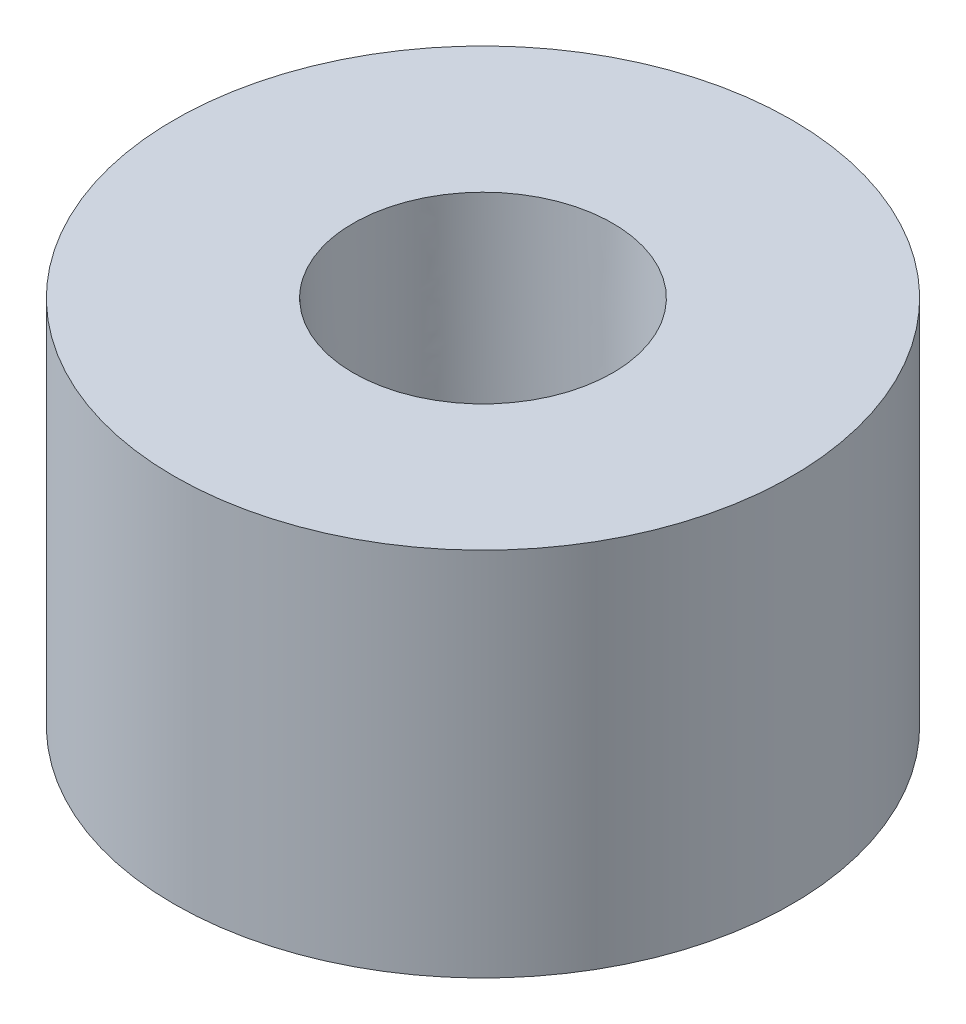
SolidWorks part; units mm, degrees
ref_plane "Frontal Plane" through (0, 0, 0) normal (0, 0, 1) x (1, 0, 0)
ref_plane "Horizontal Plane" through (0, 0, 0) normal (0, 1, 0) x (1, 0, 0)
ref_plane "Profile Plane" through (0, 0, 0) normal (1, 0, 0) x (0, 0, -1)
sketch "Sketch1" plane through (0, 0, 0) normal (0, 1, 0) x (1, 0, 0)
  circle A0 centre (0, 0) radius 12.5
  circle A1 centre (0, 0) radius 5
  dimension "D1" = 10
  dimension "D2" = 25
extrude "Boss-Extrude1" add sketch "Sketch1" along normal blind 15
sketch "Sketch2" plane through (0, 15, 0) normal (0, 1, 0) x (1, 0, 0)
  circle A0 centre (0, 0) radius 5.25
  dimension "D1" = 10.5
ref_plane "Plane1" through (0, 0, 0) normal (0, -1, 0) x (-1, 0, 0)
sketch "Sketch3" plane through (0, 0, 0) normal (0, -1, 0) x (-1, 0, 0)
  circle A0 centre (0, 0) radius 5 construction
  circle A1 centre (0, 0) radius 5
loft "Cut-Loft1" cut profiles "Sketch3", "Sketch2" connector at (4.0284, 0, -2.9618) connector at (4.7433, 15, -2.2503)
sketch "Sketch4" plane through (0, 15, 0) normal (0, 1, 0) x (1, 0, 0)
  line L0 (0, 1.5) -> (0, -1.5)
  line L1 (0, -1.5) -> (12.4097, -1.5)
  line L2 (0, 1.5) -> (12.4097, 1.5)
  circle A0 centre (0, 0) radius 12.5 construction
  arc A1 (12.4097, -1.5) -> (12.4097, 1.5) centre (0, 0) ccw
  point P5 (0, 0)
  dimension "D1" = 3
extrude "Cut-Extrude1" [suppressed] cut sketch "Sketch4" against normal through all
